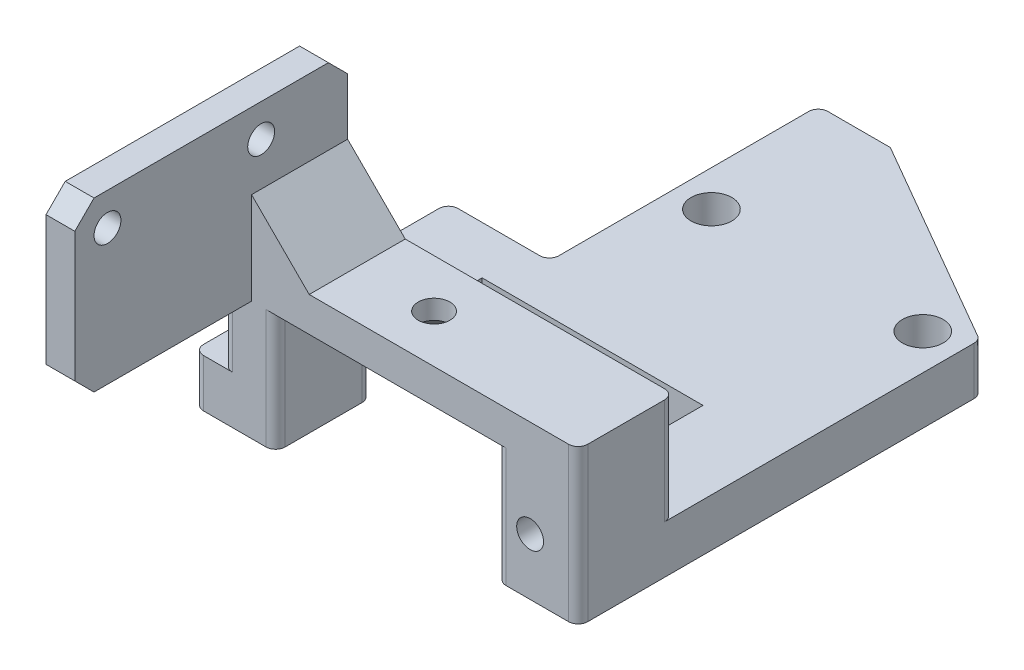
SolidWorks part; units mm, degrees
note: The reader was unsure of these and kept them because the rebuilt part matched: shared geometry of "Sketch6<3>".
ref_plane "Front Plane" through (0, 0, 0) normal (0, 0, 1) x (1, 0, 0)
ref_plane "Top Plane" through (0, 0, 0) normal (0, 1, 0) x (1, 0, 0)
ref_plane "Right Plane" through (0, 0, 0) normal (1, 0, 0) x (0, 0, -1)
sketch "Sketch2" plane through (0, 0, 0) normal (0, 0, 1) x (1, 0, 0)
  line L1 (-11.5, 6.2) -> (11.5, 6.2) construction
  line L2 (-11.5, 6.2) -> (-11.5, -6.2) construction
  line L3 (-11.5, -6.2) -> (11.5, -6.2) construction
  line L4 (11.5, 6.2) -> (11.5, -6.2) construction
  line L5 (-11.5, 6.2) -> (11.5, -6.2) construction
  line L6 (-11.5, -6.2) -> (11.5, 6.2) construction
  line L7 (11.5, -6.2) -> (20, -6.2)
  line L8 (11.5, -6.2) -> (11.5, 6.2)
  line L10 (20, -6.2) -> (20, 9.8)
  line L11 (11.5, 6.2) -> (-11.5, 6.2)
  line L13 (20, 9.8) -> (-20, 9.8)
  line L16 (-11.5, 6.2) -> (-11.5, -6.2)
  line L17 (-11.5, -6.2) -> (-20, -6.2)
  line L18 (-20, 9.8) -> (-20, -6.2)
  point P0 (0, 0)
  dimension "D1" = 23
  dimension "D2" = 12.4
  dimension "D3" = 40
  dimension "D4" = 16
extrude "Boss-Extrude1" add sketch "Sketch2" against normal blind 10
sketch "Sketch5" plane through (0, 0, 0) normal (0, 0, 1) x (1, 0, 0)
  line L0 (11.5, 6.2) -> (15, 6.2) construction
  line L1 (15, 6.2) -> (15, -6.2) construction
  line L2 (-20, -6.2) -> (-11.5, -6.2) construction
  circle A0 centre (15, -0.3) radius 1.4
  point P14 (15, 0)
  dimension "D1" = 15
  dimension "D2" = 2.8
  dimension "D3" = 0.3
extrude "Cut-Extrude2" cut sketch "Sketch5" against normal blind 6
sketch "Sketch4" plane through (0, -6.2, 0) normal (0, -1, 0) x (1, 0, 0)
  line L0 (-11.5, -5) -> (-17.25, -5) construction
  line L1 (-11.5, -10) -> (-11.5, 0) construction
  line L2 (11.5, -5) -> (17.25, -5) construction
  line L3 (11.5, -10) -> (11.5, 0) construction
  circle A0 centre (-17.25, -5) radius 1.75
  circle A1 centre (17.25, -5) radius 1.75
  dimension "D1" = 34.5
  dimension "D2" = 3.5
extrude "Cut-Extrude1" cut sketch "Sketch4" against normal blind 4.5
sketch "Sketch6" plane through (0, -6.2, 0) normal (0, -1, 0) x (1, 0, 0)
  line L0 (-17.25, -5) -> (-17.25, -28.5) construction
  line L1 (-17.25, -28.5) -> (-5.75, -28.5) construction
  line L2 (-5.75, -28.5) -> (-5.75, -50.75) construction
  line L3 (20, -10) -> (20, 0) construction
  line L4 (-20, -10) -> (-11.5, -10)
  line L5 (-20, -10) -> (-20, -21.5)
  line L6 (-20, -21.5) -> (-11.5, -21.5)
  line L7 (-11.5, -10) -> (-11.5, -21.5)
  line L8 (-9.5, -54.5) -> (-2, -54.5)
  line L9 (-9.5, -54.5) -> (-9.5, -24.75)
  line L10 (-9.5, -24.75) -> (-2, -24.75)
  line L11 (-2, -54.5) -> (-2, -24.75)
  line L12 (-9.5, -54.5) -> (-2, -24.75) construction
  line L13 (-9.5, -24.75) -> (-2, -54.5) construction
  line L14 (11.5, -10) -> (20, -10)
  line L15 (11.5, -10) -> (11.5, -21.5)
  line L16 (11.5, -21.5) -> (20, -21.5)
  line L17 (20, -10) -> (20, -21.5)
  line L18 (-11.5, -21.5) -> (11.5, -21.5)
  line L19 (-20, -21.5) -> (-20, -26.5)
  line L20 (-20, -26.5) -> (-9.5, -26.5)
  line L21 (-2, -24.75) -> (20, -24.75)
  line L22 (20, -24.75) -> (20, -21.5)
  line L23 (20, -24.75) -> (20, -41.7893)
  line L24 (-5.75, -52.5) -> (-5.75, -54.5) construction
  line L25 (20, -41.7893) -> (-2, -54.5)
  line L26 (-7.5, -50.75) -> (-9.5, -50.75) construction
  line L27 (-5.75, -39.625) -> (-9.5, -39.625) construction
  line L28 (16.25, -39.625) -> (20, -39.625) construction
  line L29 (16.25, -39.625) -> (18.126, -42.872) construction
  circle A0 centre (-5.75, -28.5) radius 1.75
  circle A1 centre (-5.75, -50.75) radius 1.75
  circle A2 centre (-17.25, -5) radius 1.75 construction
  circle A3 centre (-5.75, -39.625) radius 2.125
  circle A4 centre (16.25, -39.625) radius 2.125
  point P14 (-5.75, -39.625)
  dimension "D4" = 11.5
  dimension "D7" = 4.25
  dimension "D1" = 23.5
  dimension "D2" = 11.5
  dimension "D3" = 22.25
  dimension "D5" = 2
  dimension "D6" = 5
extrude "Boss-Extrude3" add sketch "Sketch6" against normal blind 5
extrude "Boss-Extrude4" add sketch "Sketch6<3>" along normal blind 1 from surface at -5 contours A1 | A0 starting at face at (-1.9091, -1.2, -26.0718)
sketch "Sketch6<3>" plane through (0, -6.2, 0) normal (0, -1, 0) x (1, 0, 0) same geometry as "Sketch6"
sketch "Sketch7" plane through (0, 0, -10) normal (0, 0, -1) x (-1, 0, 0)
  line L0 (11.5, -1.2) -> (11.5, -6.2)
  line L3 (11.5, -1.2) -> (20, -1.2)
  line L4 (11.5, -6.2) -> (15.5, -6.2)
  line L5 (15.5, -6.2) -> (20, -1.2)
  line L6 (20, -1.2) -> (20, -6.2) construction
  line L7 (20, -1.2) -> (9.5, -1.2) construction
  dimension "D2" = 4
extrude "Cut-Extrude3" cut sketch "Sketch7" along normal blind 5
sketch "Sketch8" plane through (-20, 0, 0) normal (-1, 0, 0) x (0, 0, 1)
  line L1 (-10, 9.8) -> (0, 9.8)
  line L2 (-10, 9.8) -> (-10, -1.2)
  line L3 (-10, -1.2) -> (0, -1.2)
  line L4 (0, 9.8) -> (0, -1.2)
  line L5 (-10, 9.8) -> (-10, -1.2) construction
extrude "Cut-Extrude4" cut sketch "Sketch8" against normal blind 3
sketch "Sketch10" plane through (-17, 0, 0) normal (-1, 0, 0) x (0, 0, 1)
  line L0 (18.4, 6.2) -> (0, 6.2)
  line L1 (0, 6.2) -> (0, -1.2)
  line L2 (-1, 20.3) -> (15, 20.3) construction
  line L3 (-1, 20.3) -> (-1, 4.3) construction
  line L4 (-1, 4.3) -> (15, 4.3) construction
  line L5 (15, 20.3) -> (15, 4.3) construction
  line L6 (-26.5, -6.2) -> (0, -6.2) construction
  line L7 (0, -1.2) -> (0, 9.8) construction
  line L8 (15, 21.7) -> (15, 23.7) construction
  line L9 (-10, -1.2) -> (18.4, -1.2)
  line L10 (-10, -1.2) -> (-10, 23.7)
  line L11 (-10, 23.7) -> (18.4, 23.7)
  line L12 (18.4, -1.2) -> (18.4, 23.7)
  line L13 (16.4, 20.3) -> (18.4, 20.3) construction
  line L14 (-10, 6.2) -> (0, 6.2) construction
  circle A0 centre (-1, 20.3) radius 1.4
  circle A1 centre (15, 20.3) radius 1.4
  circle A4 centre (-1, 4.3) radius 1.4
  dimension "D5" = 2
  dimension "D7" = 2.8
  dimension "D1" = 16
  dimension "D2" = 26.5
  dimension "D3" = 1
extrude "Boss-Extrude5" add sketch "Sketch10" against normal blind 3
chamfer "Chamfer1" distance 2 angle 45 3 edges at (-15.5, 23.7, -10) (-15.5, 23.7, 18.4) (-15.5, 6.2, 18.4)
fillet "Fillet1" radius 1 13 edges at (-11.5, -3.7, -15) (20, 1.8, 0) (-20, -3.7, 0) (11.5, 0, 0) (-17, 2.5, 0) (-11.5, 0, -10) (20, 4.3, -10) (-9.5, -3.7, -54.5) (-9.5, -3.7, -26.5) (-20, -3.7, -26.5) (20, -3.7, -41.7893) (11.5, 2.5, -10) (-11.5, 0, 0)
chamfer "Chamfer2" distance 1.35 angle 45 2 edges at (-5.75, -6.2, -41.75) (16.25, -6.2, -41.75)
chamfer "Chamfer3" distance 6 angle 45 1 edges at (-14, 9.8, -5)
sketch "Sketch12" plane through (0, 6.2, 0) normal (0, -1, 0) x (1, 0, 0)
  line L0 (0, 0) -> (0, -10) construction
  line L1 (-12.5, -10) -> (12.5, -10) construction
  circle A0 centre (0, -5) radius 1.65
  dimension "D1" = 3.3
extrude "Cut-Extrude6" cut sketch "Sketch12" against normal through all
chamfer "Chamfer4" distance 1.6 angle 45 1 edges at (0, 6.2, -6.65)
